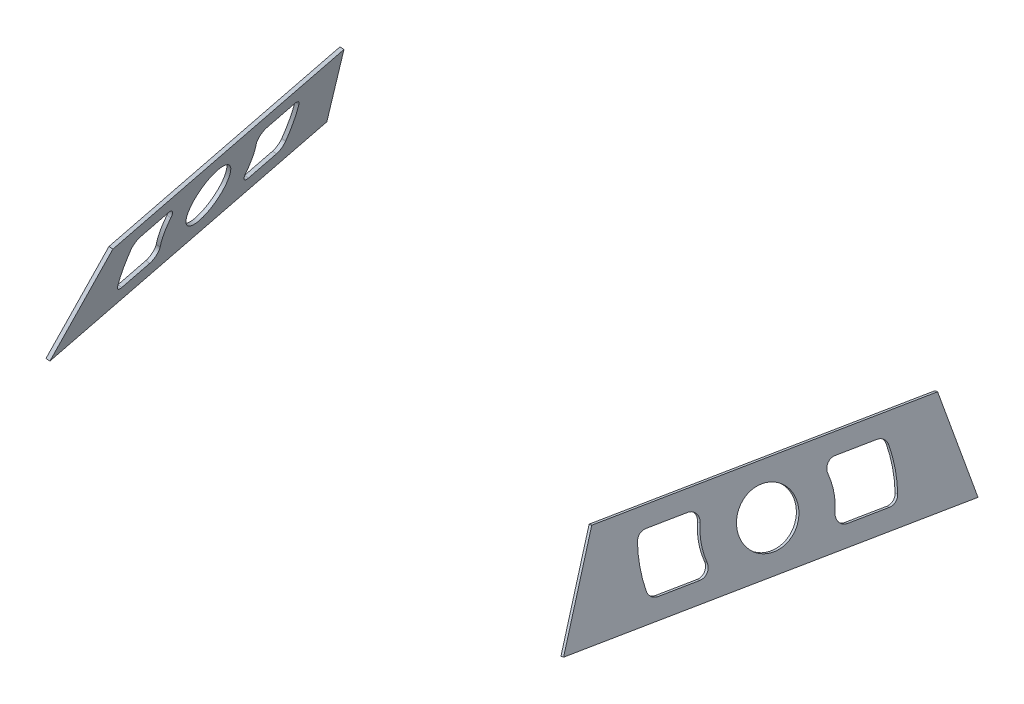
SolidWorks part; units mm, degrees
material "AISI 4130 Steel, normalized at 870C"
ref_plane "Front Plane" through (0, 0, 0) normal (0, 0, 1) x (1, 0, 0)
ref_plane "Top Plane" through (0, 0, 0) normal (0, 1, 0) x (1, 0, 0)
ref_plane "Right Plane" through (0, 0, 0) normal (1, 0, 0) x (0, 0, -1)
ref_plane "Plane1" through (-647.7275, 206.835, 128.8296) normal (0.936, -0.2989, -0.1862) x (-0.1773, 0.0566, -0.9825)
ref_plane "Plane2" through (-659.6142, 210.6307, 131.1938) normal (0.936, -0.2989, -0.1862) x (-0.1773, 0.0566, -0.9825)
sketch "Sketch1" plane through (-659.6142, 210.6307, 131.1938) normal (0.936, -0.2989, -0.1862) x (-0.1773, 0.0566, -0.9825)
  line L0 (-1393.9313, 796.4424) -> (-1387.1074, 745.9484)
  line L1 (-1387.1074, 745.9484) -> (-1589.6785, 757.9902)
  line L2 (-1589.6785, 757.9902) -> (-1562.979, 806.4913)
  line L3 (-1562.979, 806.4913) -> (-1393.9313, 796.4424)
  line L4 (-1868.8378, 250.8817) -> (-1428.3419, 1051.0671) construction
  line L10 (-1428.3419, 1051.0671) -> (-1321.2913, 258.9362) construction
  line L11 (-1544.2893, 840.4421) -> (-1398.708, 831.7881) construction
  point P20 (-1471.4987, 836.1151)
  dimension "D1" = 50
  dimension "D2" = 35
extrude "Boss-Extrude1" add sketch "Sketch1" against normal blind 2
sketch "Sketch3" plane through (-647.7275, 206.835, 128.8296) normal (0.936, -0.2989, -0.1862) x (-0.1773, 0.0566, -0.9825)
  line L0 (-1390.5193, 771.1954) -> (-1576.3287, 782.2408) construction
  line L1 (-1393.9313, 796.4424) -> (-1387.1074, 745.9484) construction
  line L2 (-1589.6785, 757.9902) -> (-1562.979, 806.4913) construction
  line L3 (-1478.4551, 801.4668) -> (-1488.3929, 751.9693) construction
  line L4 (-1562.979, 806.4913) -> (-1393.9313, 796.4424) construction
  line L5 (-1387.1074, 745.9484) -> (-1589.6785, 757.9902) construction
  circle A0 centre (-1483.424, 776.7181) radius 15
  dimension "D1" = 30
extrude "Cut-Extrude4" cut sketch "Sketch3" along normal through all both and the other way through all contours A0
sketch "Sketch5" plane through (-661.4861, 211.2284, 131.5661) normal (-0.936, 0.2989, 0.1862) x (0.3518, 0.7718, 0.5297)
  circle A0 centre (1507.3574, 801.7343) radius 19.9414 construction
  circle A1 centre (1507.3574, 801.7343) radius 19.9414
  circle A2 centre (1507.358, 801.7066) radius 14.4575 construction
  circle A3 centre (1507.358, 801.7066) radius 14.4575
split line "Split Line1" [suppressed]
sketch "Sketch6" plane through (-661.4861, 211.2284, 131.5661) normal (-0.936, 0.2989, 0.1862) x (0.1773, -0.0566, 0.9825)
  line L0 (1393.9313, 796.4424) -> (1562.979, 806.4913) construction
  line L1 (1446.5748, 789.5541) -> (1426.1168, 788.338)
  line L2 (1427.8536, 758.3882) -> (1448.2869, 759.6029)
  line L4 (1589.6785, 757.9902) -> (1387.1074, 745.9484) construction
  line L5 (1518.6631, 793.8393) -> (1539.1211, 795.0555)
  line L6 (1520.5113, 763.8962) -> (1540.9447, 765.1109)
  circle A0 centre (1483.5163, 776.6002) radius 15 construction
  arc A1 (1451.7574, 783.5012) -> (1452.7271, 766.1949) centre (1483.5163, 776.6002) ccw
  arc A2 (1421.448, 783.9334) -> (1422.6908, 762.2298) centre (1483.5163, 776.6002) ccw
  arc A3 (1515.3215, 769.9158) -> (1514.234, 787.2151) centre (1483.5163, 776.6002) ccw
  arc A4 (1545.6159, 769.537) -> (1544.2787, 791.2351) centre (1483.5163, 776.6002) ccw
  arc A5 (1520.5113, 763.8962) -> (1515.3215, 769.9158) centre (1520.2146, 768.8874) cw
  arc A6 (1540.9447, 765.1109) -> (1545.6159, 769.537) centre (1540.648, 770.1021) ccw
  arc A7 (1539.1211, 795.0555) -> (1544.2787, 791.2351) centre (1539.4178, 790.0643) cw
  arc A8 (1518.6631, 793.8393) -> (1514.234, 787.2151) centre (1518.9598, 788.8481) ccw
  arc A9 (1427.8536, 758.3882) -> (1422.6908, 762.2298) centre (1427.5569, 763.3794) cw
  arc A10 (1448.2869, 759.6029) -> (1452.7271, 766.1949) centre (1447.9902, 764.5941) ccw
  arc A11 (1451.7574, 783.5012) -> (1446.5748, 789.5541) centre (1446.8715, 784.5629) ccw
  arc A12 (1426.1168, 788.338) -> (1421.448, 783.9334) centre (1426.4135, 783.3468) ccw
  point P0 (1483.5163, 776.6002)
  point P18 (1513.2433, 763.4642)
  point P21 (1544.9958, 765.3517)
  dimension "D1" = 65
  dimension "D2" = 125
  dimension "D7" = 5
  dimension "D3" = 10
  dimension "D4" = 10
  dimension "D5" = 10
  dimension "D6" = 10
extrude "Cut-Extrude5" cut sketch "Sketch6" against normal through all both and the other way through all
mirror "Mirror5" about plane through (0, 0, 0) normal (1, 0, 0) of bodies 107
